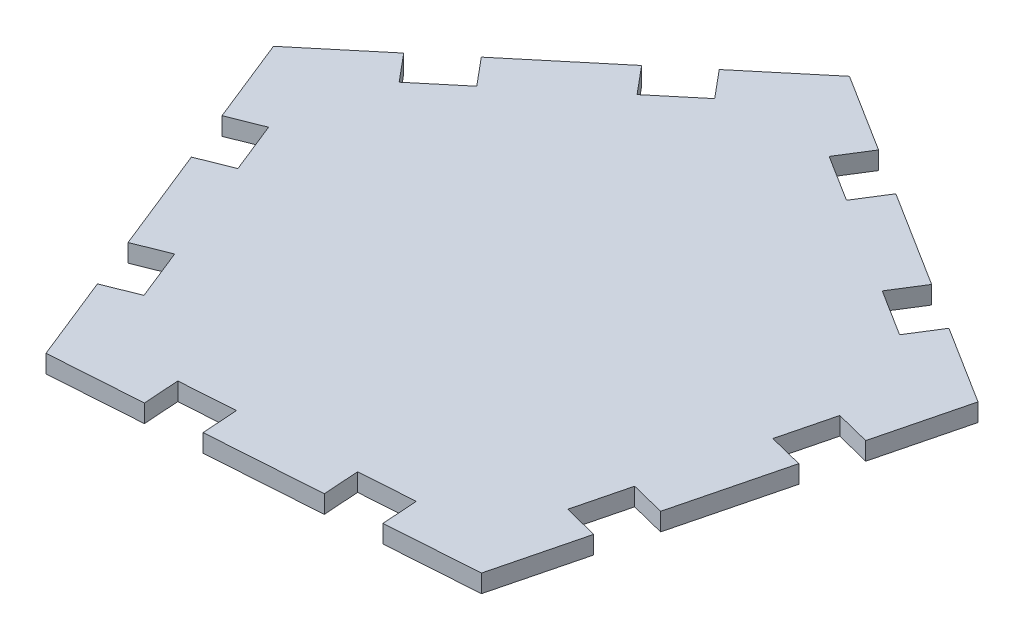
SolidWorks part; units mm, degrees
ref_plane "Front Plane" through (0, 0, 0) normal (0, 0, 1) x (1, 0, 0)
ref_plane "Top Plane" through (0, 0, 0) normal (0, 1, 0) x (1, 0, 0)
ref_plane "Right Plane" through (0, 0, 0) normal (1, 0, 0) x (0, 0, -1)
sketch "Sketch1" plane through (0, 0, 0) normal (0, 1, 0) x (1, 0, 0)
  line L1 (-59.9258, 15.1181) -> (-32.8962, -52.3211)
  line L2 (-32.8962, -52.3211) -> (39.5948, -47.4543)
  line L3 (39.5948, -47.4543) -> (57.3672, 22.9927)
  line L4 (57.3672, 22.9927) -> (-4.14, 61.6646)
  line L5 (-4.14, 61.6646) -> (-59.9258, 15.1181)
  circle A0 centre (0, 0) radius 50 construction
  dimension "D1" = 100
extrude "Boss-Extrude1" add sketch "Sketch1" along normal blind 3.18
ref_axis "Axis" through (0, 3.339, 0) along (0, -1, 0)
sketch "Axis Check" [suppressed] plane through (0, 3.18, 0) normal (0, 1, 0) x (1, 0, 0)
  line L0 (3.3493, -49.8877) -> (-4.14, 61.6646) construction
  line L1 (-32.8962, -52.3211) -> (39.5948, -47.4543) construction
  line L2 (57.3672, 22.9927) -> (-46.411, -18.6015) construction
  line L3 (-59.9258, 15.1181) -> (-32.8962, -52.3211) construction
  line L4 (-32.0329, 38.3913) -> (39.5948, -47.4543) construction
  line L5 (-4.14, 61.6646) -> (-59.9258, 15.1181) construction
  line L6 (-59.9258, 15.1181) -> (48.481, -12.2308) construction
  line L7 (39.5948, -47.4543) -> (57.3672, 22.9927) construction
  line L8 (-32.8962, -52.3211) -> (26.6136, 42.3287) construction
  line L9 (57.3672, 22.9927) -> (-4.14, 61.6646) construction
sketch "Sketch2" plane through (0, 0, 0) normal (0, -1, 0) x (1, 0, 0)
  line L0 (-53.8144, 0.1299) -> (-47.9109, -2.2362)
  line L1 (-53.8144, 0.1299) -> (-50.1723, 9.2172)
  line L2 (-47.9109, -2.2362) -> (-44.2688, 6.8511)
  line L3 (-50.1723, 9.2172) -> (-44.2688, 6.8511)
  line L4 (-59.9258, -15.1181) -> (-32.8962, 52.3211) construction
  line L5 (-42.6498, 27.9858) -> (-39.0076, 37.0731)
  line L6 (-42.6498, 27.9858) -> (-36.7463, 25.6197)
  line L7 (-39.0076, 37.0731) -> (-33.1041, 34.707)
  line L8 (-36.7463, 25.6197) -> (-33.1041, 34.707)
  line L9 (-46.411, 18.6015) -> (-19.2439, 7.7129) construction
  line L10 (-40.8287, 32.5295) -> (-34.9252, 30.1634) construction
  dimension "D1" = 6.36
  dimension "D3" = 10.11
  dimension "D2" = 9.79
extrude "Cut F" cut sketch "Sketch2" against normal through all
sketch "Sketch4" [suppressed] plane through (0, 3.18, 0) normal (0, 1, 0) x (1, 0, 0)
  line L9 (26.6136, 42.3287) -> (-26.6136, -42.3287) construction
  line L10 (57.3672, 22.9927) -> (-4.14, 61.6646) construction
  line L11 (-34.4964, -17.2915) -> (0.6335, 38.5824)
  line L12 (-34.4964, -17.2915) -> (-0.6335, -38.5824)
  line L13 (0.6335, 38.5824) -> (34.4964, 17.2915)
  line L14 (-0.6335, -38.5824) -> (34.4964, 17.2915)
  line L15 (-34.4964, -17.2915) -> (34.4964, 17.2915) construction
  line L16 (0.6335, 38.5824) -> (-0.6335, -38.5824) construction
  line L20 (0, 0) -> (39.0006, -24.5211) construction
  circle A0 centre (-21.8232, -34.7095) radius 3.25
  circle A1 centre (23.7041, -14.9036) radius 3.25
  point P5 (0, 0)
  point P6 (-21.8232, -34.7095)
  dimension "D3" = 6.5
  dimension "D1" = 40
  dimension "D2" = 66
  dimension "D4" = 8
  dimension "D5" = 8
extrude "Top Cut" [suppressed] cut sketch "Sketch4" against normal blind 10
sketch "Sketch7" [suppressed] plane through (0, 3.18, 0) normal (0, 1, 0) x (1, 0, 0)
  line L0 (0, 0) -> (26.6136, 42.3287) construction
  line L1 (57.3672, 22.9927) -> (-4.14, 61.6646) construction
  line L2 (-7.1857, -11.4287) -> (-30.8897, 3.4749) construction
  line L3 (-14.3588, -11.6437) -> (-33.0188, 0.0886) construction
  line L5 (0.6335, 38.5824) -> (-34.4964, -17.2915) construction
  circle A0 centre (-30.8897, 3.4749) radius 1
  circle A1 centre (-33.0188, 0.0886) radius 1
  dimension "D5" = 2
  dimension "D1" = 4
  dimension "D2" = 17.5
  dimension "D3" = 8
  dimension "D4" = 8
extrude "Top Cut 2" [suppressed] cut sketch "Sketch7" against normal through all
sketch "Sketch10" [suppressed] plane through (0, 3.18, 0) normal (0, 1, 0) x (1, 0, 0)
  line L0 (26.6136, 42.3287) -> (17.565, 27.9369) construction
  line L1 (57.3672, 22.9927) -> (-4.14, 61.6646) construction
  line L2 (34.4964, 17.2915) -> (0.6335, 38.5824) construction
  line L3 (33.0578, 31.7802) -> (13.6147, 44.0048) construction
  line L4 (34.4964, 17.2915) -> (0.6335, 38.5824) construction
  circle A0 centre (19.4532, 40.3339) radius 1
  circle A1 centre (27.919, 35.0111) radius 1
  dimension "D1" = 11.5
  dimension "D2" = 2
  dimension "D3" = 5
extrude "Top Cut 3" [suppressed] cut sketch "Sketch10" against normal blind 10
sketch "Sketch8" [suppressed] plane through (0, 3.18, 0) normal (0, 1, 0) x (1, 0, 0)
  line L0 (3.3493, -49.8877) -> (-4.14, 61.6646) construction
  line L5 (-32.8962, -52.3211) -> (39.5948, -47.4543) construction
  line L6 (-17.9455, -31.2723) -> (21.9647, -28.5929)
  line L11 (-17.9455, -31.2723) -> (-21.9647, 28.5929)
  line L12 (21.9647, -28.5929) -> (17.9455, 31.2723)
  line L13 (-21.9647, 28.5929) -> (17.9455, 31.2723)
  point P4 (1.4955, -22.2759)
  dimension "D1" = 60
  dimension "D2" = 40
  dimension "D3" = 20
extrude "Bottom Cut" [suppressed] cut sketch "Sketch8" against normal blind 10
sketch "Sketch9" [suppressed] plane through (0, 3.18, 0) normal (0, 1, 0) x (1, 0, 0)
  line L0 (19.9551, 1.3397) -> (-19.9551, -1.3397) construction
  line L1 (21.9647, -28.5929) -> (17.9455, 31.2723) construction
  line L2 (-21.9647, 28.5929) -> (-17.9455, -31.2723) construction
  line L3 (-19.9551, -1.3397) -> (-44.4689, -2.9855) construction
  line L4 (19.9551, 1.3397) -> (42.6839, 2.8657) construction
  line L5 (-32.8962, -52.3211) -> (39.5948, -47.4543) construction
  line L6 (-29.6051, -6.8886) -> (-32.3788, -7.0748)
  line L7 (-29.6051, -6.8886) -> (-30.2602, 2.8694)
  line L8 (-30.2602, 2.8694) -> (-33.0339, 2.6832)
  line L9 (-32.3788, -7.0748) -> (-33.0339, 2.6832)
  line L10 (-29.6051, -6.8886) -> (-33.0339, 2.6832) construction
  line L11 (-30.2602, 2.8694) -> (-32.3788, -7.0748) construction
  line L12 (33.0339, -2.6832) -> (30.2602, -2.8694)
  line L13 (33.0339, -2.6832) -> (32.3788, 7.0748)
  line L14 (32.3788, 7.0748) -> (29.6051, 6.8886)
  line L15 (30.2602, -2.8694) -> (29.6051, 6.8886)
  line L16 (33.0339, -2.6832) -> (29.6051, 6.8886) construction
  line L17 (32.3788, 7.0748) -> (30.2602, -2.8694) construction
  line L18 (-32.8962, -52.3211) -> (39.5948, -47.4543) construction
  point P6 (-31.3195, -2.1027)
  point P13 (31.3195, 2.1027)
  dimension "D1" = 9.81
  dimension "D4" = 9.81
  dimension "D5" = 10
  dimension "D6" = 10
  dimension "D2" = 2.78
  dimension "D3" = 2.78
extrude "Battery Holder Cut" [suppressed] cut sketch "Sketch9" against normal blind 6.36
sketch "Sketch3" [suppressed] plane through (0, 3.18, 0) normal (0, 1, 0) x (1, 0, 0)
  line L0 (0, 0) -> (-40.9819, 49.1167) construction
  line L1 (-51.5408, 30.3975) -> (-43.3916, 20.6307)
  line L3 (-43.3916, 20.6307) -> (-35.5521, 27.1718)
  line L4 (-43.7013, 36.9386) -> (-35.5521, 27.1718)
  line L5 (-4.14, 61.6646) -> (-59.9258, 15.1181) construction
  line L6 (-71.9961, 5.0469) -> (-69.9588, 2.6052)
  line L7 (-71.9961, 5.0469) -> (-47.4739, 25.5077)
  line L14 (-28.5137, 49.6108) -> (-20.3645, 39.8441)
  line L16 (-20.3645, 39.8441) -> (-12.525, 46.3852)
  line L17 (-20.6742, 56.1519) -> (-12.525, 46.3852)
  line L18 (-40.4979, 25.131) -> (-39.4719, 23.9013) construction
  line L19 (-51.5408, 30.3975) -> (-43.7013, 36.9386)
  line L21 (-28.5137, 49.6108) -> (-20.6742, 56.1519)
  line L22 (-16.5996, 51.2685) -> (4.7866, 69.1127)
  line L23 (-39.6267, 32.0552) -> (-24.4391, 44.7274)
  line M18 (-4.14, 61.6646) -> (-59.9258, 15.1181)
  dimension "D1" = 12.72
  dimension "D2" = 10.21
  dimension "D3" = 9.89
  dimension "D4" = 100
extrude "Extrude M" [suppressed] add sketch "Sketch3" against normal up to surface (3.18 mm away) contours L21 L14 L7 L17 | L19 L1 L4 M18 up to face at (-26.7442, 0, 10.7191)
pattern_circular "Circle F" count 5 over 360 about axis through (0, 3.339, 0) along (0, -1, 0) of "Cut F"
pattern_circular "Circle M" [suppressed] count 5 over 360 about axis through (0, 3.339, 0) along (0, -1, 0) of bodies 173
pattern_circular "Circle Side F" [suppressed] count 5 over 360 about axis through (0, 3.339, 0) along (0, -1, 0) of bodies 173
pattern_circular "Circle Side M" [suppressed] count 5 over 360 about axis through (0, 3.339, 0) along (0, -1, 0) of bodies 168
equation "\"kerf\" = .19mm"
equation "\"tabWidthF\"= 10 - \"kerf\""
equation "\"tabThickness\" = 6.36mm"
equation "\"D1@Sketch2\"=\"tabThickness\""
equation "\"tabWidthM\"= 10 + \"kerf\""
equation "\"halfkerf\"= \"kerf\" / 2.00mm"
equation "\"D1@Sketch9\"=\"tabWidthF\""
equation "\"D4@Sketch9\"=\"tabWidthF\""
equation "\"D1@Battery Holder Cut\" = \"tabThickness\""
equation "\"tabLength\" = \"kerf\" + 12"
